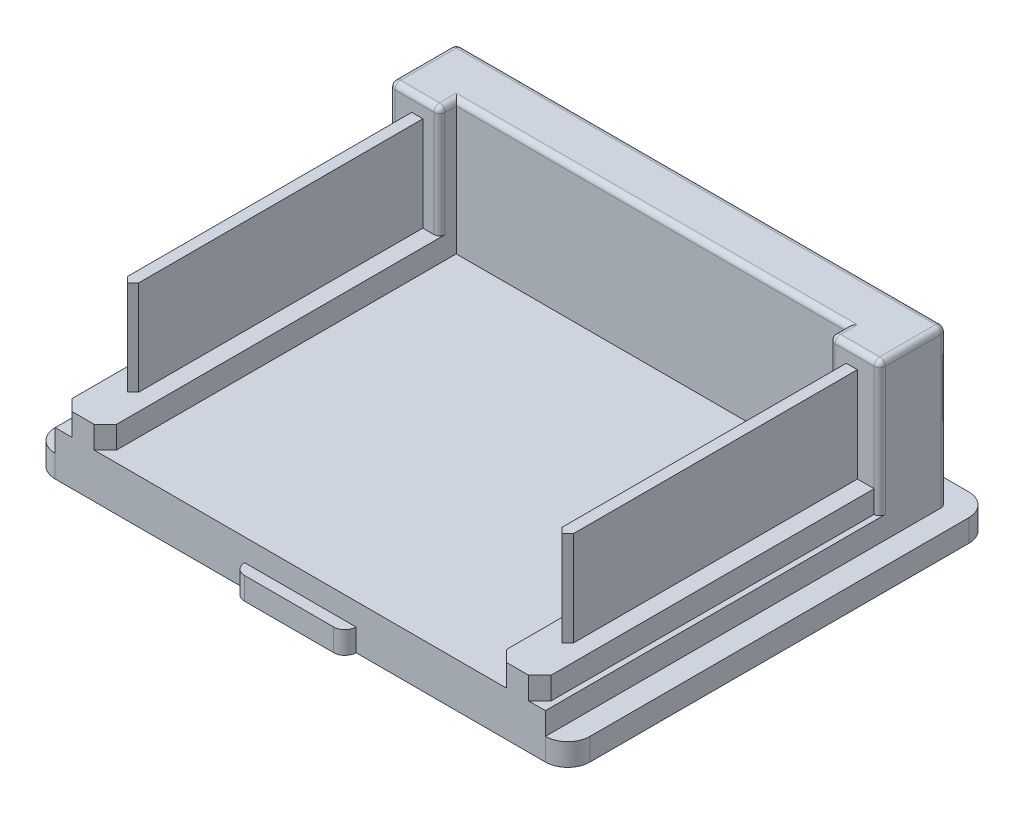
SolidWorks part; units mm, degrees
ref_plane "Front Plane" through (0, 0, 0) normal (0, 0, 1) x (1, 0, 0)
ref_plane "Top Plane" through (0, 0, 0) normal (0, 1, 0) x (1, 0, 0)
ref_plane "Right Plane" through (0, 0, 0) normal (1, 0, 0) x (0, 0, -1)
sketch "Sketch1" plane through (0, 0, 0) normal (0, 1, 0) x (1, 0, 0)
  line L1 (-24, 19) -> (24, 19)
  line L2 (-24, 19) -> (-24, -19)
  line L3 (-24, -19) -> (24, -19)
  line L4 (24, 19) -> (24, -19)
  line L5 (-24, 19) -> (24, -19) construction
  line L6 (-24, -19) -> (24, 19) construction
  point P0 (0, 0)
  dimension "D1" = 48
  dimension "D2" = 38
extrude "Boss-Extrude1" add sketch "Sketch1" along normal blind 2
sketch "Sketch2" plane through (0, 2, 0) normal (0, 1, 0) x (1, 0, 0)
  line L0 (-24, -19) -> (24, -19) construction
  line L1 (-22, -19) -> (22, -19)
  line L2 (-22, -19) -> (-22, 17)
  line L3 (-22, 17) -> (22, 17)
  line L4 (22, -19) -> (22, 17)
  line L5 (0, 0) -> (0, 19) construction
  line L6 (24, 19) -> (-24, 19) construction
  dimension "D1" = 36
  dimension "D2" = 44
  dimension "D3" = 22
extrude "Boss-Extrude2" add sketch "Sketch2" along normal blind 2
sketch "Sketch3" plane through (0, 4, 0) normal (0, 1, 0) x (1, 0, 0)
  line L0 (-22, -19) -> (22, -19) construction
  line L1 (-21.5, -19) -> (21.5, -19)
  line L2 (-21.5, -19) -> (-21.5, 11)
  line L3 (-21.5, 11) -> (21.5, 11)
  line L4 (21.5, -19) -> (21.5, 11)
  line L5 (0, 0) -> (0, -19) construction
  line L6 (22, 17) -> (-22, 17) construction
  line L7 (-21.5, -19) -> (-17.5, -19)
  line L8 (-21.5, -19) -> (-21.5, 11)
  line L9 (-21.5, 11) -> (-17.5, 11)
  line L10 (-17.5, -19) -> (-17.5, 11)
  line L11 (21.5, -19) -> (17.5, -19)
  line L12 (21.5, -19) -> (21.5, 11)
  line L13 (21.5, 11) -> (17.5, 11)
  line L14 (17.5, -19) -> (17.5, 11)
  line L15 (22, -19) -> (22, 17) construction
  line L16 (-22, 17) -> (-22, -19) construction
  line L17 (22, -19) -> (22, 17)
  line L18 (22, 17) -> (-22, 17)
  line L19 (-22, 17) -> (-22, -19)
  line L21 (-21.5, 11) -> (21.5, 11)
  line L22 (-21.5, 11) -> (-21.5, 15.5)
  line L23 (-21.5, 15.5) -> (21.5, 15.5)
  line L24 (21.5, 11) -> (21.5, 15.5)
  line M16 (-22, -19) -> (22, -19)
  dimension "D1" = 43
  dimension "D2" = 4
  dimension "D3" = 4
  dimension "D4" = 6
  dimension "D5" = 4.5
extrude "Boss-Extrude3" add sketch "Sketch3" along normal blind 2 contours L10 L3 L2 M16 | L14 L4 L3 M16
chamfer "Chamfer1" distance 1 angle 45 4 edges at (-21.5, 5, 19) (-17.5, 5, 19) (17.5, 5, 19) (21.5, 5, 19)
sketch "Sketch4" plane through (0, 4, 0) normal (0, 1, 0) x (1, 0, 0)
  line L0 (22, -19) -> (22, 17) construction
  line L1 (-22, 17) -> (22, 17)
  line L2 (-22, 17) -> (-22, 11)
  line L3 (-22, 11) -> (22, 11)
  line L4 (22, 17) -> (22, 11)
  line L5 (17.5, 11) -> (21.5, 11) construction
  line L6 (17.5, -18) -> (17.5, 11) construction
  line L7 (-17.5, 11) -> (17.5, 11)
  line L8 (-17.5, 11) -> (-17.5, 12.5)
  line L9 (-17.5, 12.5) -> (17.5, 12.5)
  line L10 (17.5, 11) -> (17.5, 12.5)
  line M12 (17.5, 11) -> (21.5, 11)
  line M16 (22, -19) -> (22, 17)
  line M17 (22, 17) -> (-22, 17)
  line M18 (-22, 17) -> (-22, -19)
  line M21 (-21.5, 11) -> (-17.5, 11)
  dimension "D1" = 1.5
extrude "Boss-Extrude4" add sketch "Sketch4" along normal blind 12 contours L10 L3 L8 L9 M12 M16 M17 M18 M21
fillet "Fillet1" radius 0.5 16 edges at (21.75, 4, -11) (17.5, 11, -11) (17.5, 16, -11.75) (22, 10, -11) (-22, 10, -11) (-21.75, 4, -11) (-17.5, 11, -11) (19.75, 16, -11) (22, 16, -14) (0, 16, -17) (-22, 16, -14) (-19.75, 16, -11) (-17.5, 16, -11.75) (0, 16, -12.5) (-22, 9, -17) (22, 9, -17)
sketch "Sketch5" plane through (0, 6, 0) normal (0, 1, 0) x (1, 0, 0)
  line L0 (-21.5, 11) -> (-18, 11) construction
  line L1 (-20, 11) -> (-19, 11)
  line L2 (-20, 11) -> (-20, -15)
  line L3 (-20, -15) -> (-19, -15)
  line L4 (-19, 11) -> (-19, -15)
  line L5 (-21.5, -18) -> (-21.5, 11) construction
  dimension "D1" = 1
  dimension "D2" = 1.5
  dimension "D3" = 26
extrude "Boss-Extrude5" add sketch "Sketch5" along normal blind 8.5
chamfer "Chamfer2" distance 0.5 angle 45 2 edges at (-19, 10.25, 15) (-20, 10.25, 15)
ref_plane "Plane1" through (0, 0, 0) normal (-1, 0, 0) x (0, 0, 1)
mirror "Mirror1" about plane through (0, 0, 0) normal (-1, 0, 0) of "Chamfer2", "Boss-Extrude5"
sketch "Sketch6" plane through (0, 0, 0) normal (0, -1, 0) x (1, 0, 0)
  line L0 (-24, 19) -> (24, 19) construction
  line L1 (5, 19) -> (-5, 19)
  line L2 (5, 19) -> (5, 20)
  line L3 (5, 20) -> (-5, 20)
  line L4 (-5, 19) -> (-5, 20)
  dimension "D1" = 10
  dimension "D2" = 1
  dimension "D3" = 5
extrude "Boss-Extrude6" add sketch "Sketch6" against normal blind 2
fillet "Fillet2" radius 1 2 edges at (-5, 1, 20) (5, 1, 20)
sketch "Sketch7" plane through (0, 0, 0) normal (0, -1, 0) x (1, 0, 0)
  line L0 (24, -19) -> (-24, -19) construction
  line L1 (10, -14) -> (-10, -14)
  line L2 (10, -14) -> (10, 1)
  line L3 (10, 1) -> (-10, 1)
  line L4 (-10, -14) -> (-10, 1)
  line L5 (0, -14) -> (0, 1) construction
  line L6 (8.1, -12.1) -> (-8.1, -12.1)
  line L7 (-8.1, -12.1) -> (-8.1, -0.9)
  line L8 (8.1, -0.9) -> (-8.1, -0.9)
  line L9 (8.1, -12.1) -> (8.1, -0.9)
  line L11 (0.95, -14) -> (-0.95, -14)
  line L12 (0.95, -14) -> (0.95, 1)
  line L13 (0.95, 1) -> (-0.95, 1)
  line L14 (-0.95, -14) -> (-0.95, 1)
  dimension "D1" = 15
  dimension "D2" = 20
  dimension "D3" = 20
  dimension "D4" = 1.9
  dimension "D5" = 1.9
  dimension "D6" = 0.95
extrude "Boss-Extrude7" add sketch "Sketch7" along normal blind 4.5 contours L1 L14 L6 L7 L8 L3 L4 | L11 L5 L6 L14 | L5 L1 L12 L6 | L12 L1 L2 L3 L8 L9 L6 | L6 L5 L8 L14 | L5 L6 L12 L8 | L8 L5 L13 L14 | L5 L8 L12 L3
sketch "Sketch8" plane through (0, -4.5, 0) normal (0, -1, 0) x (1, 0, 0)
  line L0 (10, -14) -> (-10, -14) construction
  line L1 (0.95, -14) -> (-0.95, -14)
  line L2 (0.95, -14) -> (0.95, 1)
  line L3 (0.95, 1) -> (-0.95, 1)
  line L4 (-0.95, -14) -> (-0.95, 1)
  line L5 (10, 1) -> (-10, 1) construction
  line L6 (-0.95, -12.1) -> (-0.95, -0.9) construction
  line L7 (0.95, -12.1) -> (0.95, -0.9) construction
  line L8 (0.95, -0.9) -> (-0.95, -0.9)
  line L9 (0.95, -12.1) -> (-0.95, -12.1)
  line M6 (0.95, -12.1) -> (0.95, -0.9)
  line M9 (-0.95, -0.9) -> (-0.95, -12.1)
extrude "Boss-Extrude8" add sketch "Sketch8" along normal blind 4 contours L9 L8 M6 M9
sketch "Sketch9" plane through (0, 0, 0) normal (0, -1, 0) x (1, 0, 0)
  line L0 (-0.95, -12.1) -> (-8.1, -12.1) construction
  line L1 (-4.025, -9.75) -> (-5.025, -9.75)
  line L2 (-4.025, -9.75) -> (-4.025, -3.25)
  line L3 (-4.025, -3.25) -> (-5.025, -3.25)
  line L4 (-5.025, -9.75) -> (-5.025, -3.25)
  line L6 (-0.95, -12.1) -> (-0.95, -0.9) construction
  dimension "D1" = 6.5
  dimension "D2" = 2.35
  dimension "D3" = 1
  dimension "D4" = 3.075
extrude "Boss-Extrude9" add sketch "Sketch9" along normal blind 9
fillet "Fillet3" radius 1 2 edges at (-4.525, -9, -3.25) (-4.525, -9, -9.75)
sketch "Sketch10" plane through (-5.025, 0, 0) normal (-1, 0, 0) x (0, 0, 1)
  line L0 (-6.5, -9) -> (-6.5, -1.8129) construction
  line L1 (-4.25, -9) -> (-8.75, -9) construction
  circle A0 centre (-6.5, -6) radius 0.75
  dimension "D1" = 3
  dimension "D2" = 1.5
extrude "Cut-Extrude1" cut sketch "Sketch10" against normal blind 2
mirror "Mirror2" about plane through (0, 0, 0) normal (-1, 0, 0) of "Fillet3", "Boss-Extrude9", "Cut-Extrude1"
sketch "Sketch11" plane through (0, 0, 0) normal (0, -1, 0) x (1, 0, 0)
  line L0 (-24, 19) -> (-5, 19) construction
  line L1 (20, -1.9) -> (-20, -1.9)
  line L2 (20, -1.9) -> (20, 17.1)
  line L3 (20, 17.1) -> (-20, 17.1)
  line L4 (-20, -1.9) -> (-20, 17.1)
  line L5 (-10, -14) -> (-10, 1) construction
  line L6 (10, 1) -> (-10, 1) construction
  line L7 (10, -14) -> (10, 1) construction
  line L8 (-10, -14) -> (-10, 1)
  line L9 (10, 1) -> (-10, 1)
  line L10 (10, -14) -> (10, 1)
  line L11 (10, -14) -> (-10, -14) construction
  line L12 (20, -15.2) -> (-20, -15.2)
  line L13 (20, -15.2) -> (20, -11.4)
  line L14 (20, -11.4) -> (-20, -11.4)
  line L15 (-20, -15.2) -> (-20, -11.4)
  line L16 (10, -14) -> (-10, -14)
  line M13 (10, 1) -> (10, -14)
  line M14 (10, -14) -> (-10, -14)
  line M15 (-10, -14) -> (-10, 1)
  line M16 (-10, 1) -> (10, 1)
  dimension "D1" = 40
  dimension "D2" = 19
  dimension "D3" = 1.9
  dimension "D4" = 20
  dimension "D5" = 9.5
  dimension "D6" = 3.8
extrude "Cut-Extrude2" cut sketch "Sketch11" against normal blind 2 contours L15 L12 L13 L14 L10 M14 M15 | L4 L1 L2 L3 M15 M16 M13
fillet "Fillet4" radius 1 2 edges at (0, -8.5, -12.1) (0, -8.5, -0.9)
fillet "Fillet5" radius 2 4 edges at (-24, 1, -19) (-24, 1, 19) (24, 1, 19) (24, 1, -19)
